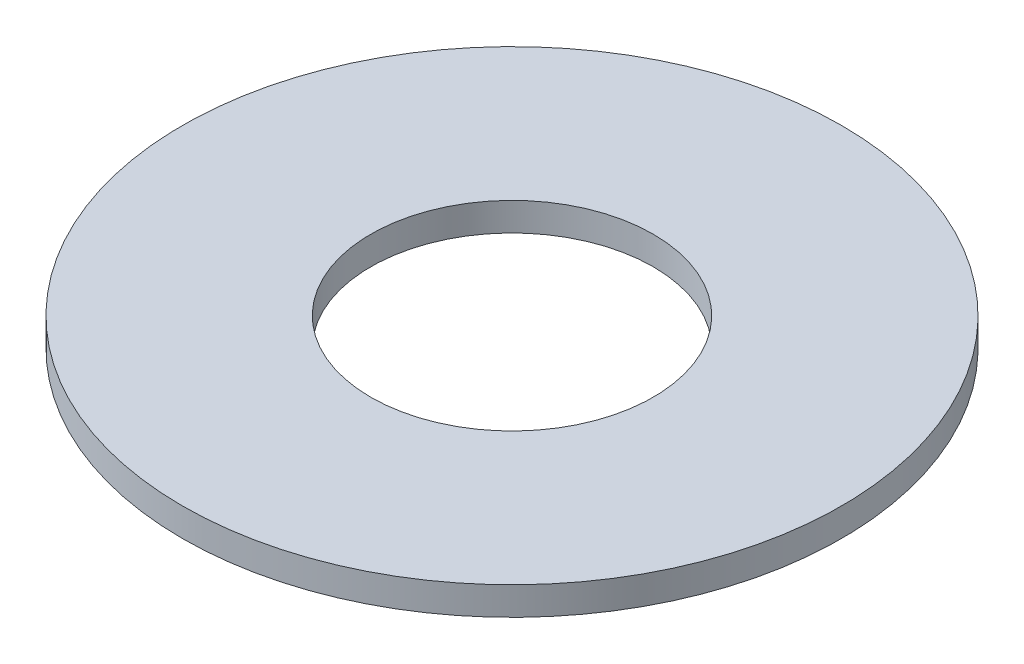
SolidWorks part; units mm, degrees
ref_plane "Front Plane" through (0, 0, 0) normal (0, 0, 1) x (1, 0, 0)
ref_plane "Top Plane" through (0, 0, 0) normal (0, 1, 0) x (1, 0, 0)
ref_plane "Right Plane" through (0, 0, 0) normal (1, 0, 0) x (0, 0, -1)
sketch "Sketch1" plane through (0, 0, 0) normal (0, 1, 0) x (1, 0, 0)
  circle A0 centre (0, 0) radius 70
  dimension "FLANGE_OD" = 140
extrude "Boss-Extrude1" add sketch "Sketch1" along normal blind 6
sketch "Sketch2" plane through (0, 0, 0) normal (0, 1, 0) x (1, 0, 0)
  circle A0 centre (0, 0) radius 30
  dimension "BORE_D" = 60
extrude "Cut-Extrude1" cut sketch "Sketch2" along normal through all
sketch "Sketch3" plane through (0, 6, 0) normal (0, 1, 0) x (1, 0, 0)
  circle A0 centre (0, 0) radius 26.3142 construction
  circle A1 centre (-26.3142, 0) radius 1.9014
  dimension "BOLT_D" = 3.8027
  dimension "BOLT_PCD" = 52.6284
extrude "Cut-Extrude2" cut sketch "Sketch3" against normal blind 4.0621 rebuild error yes
pattern_circular "CirPattern1" count 6 over 360 rebuild error yes
